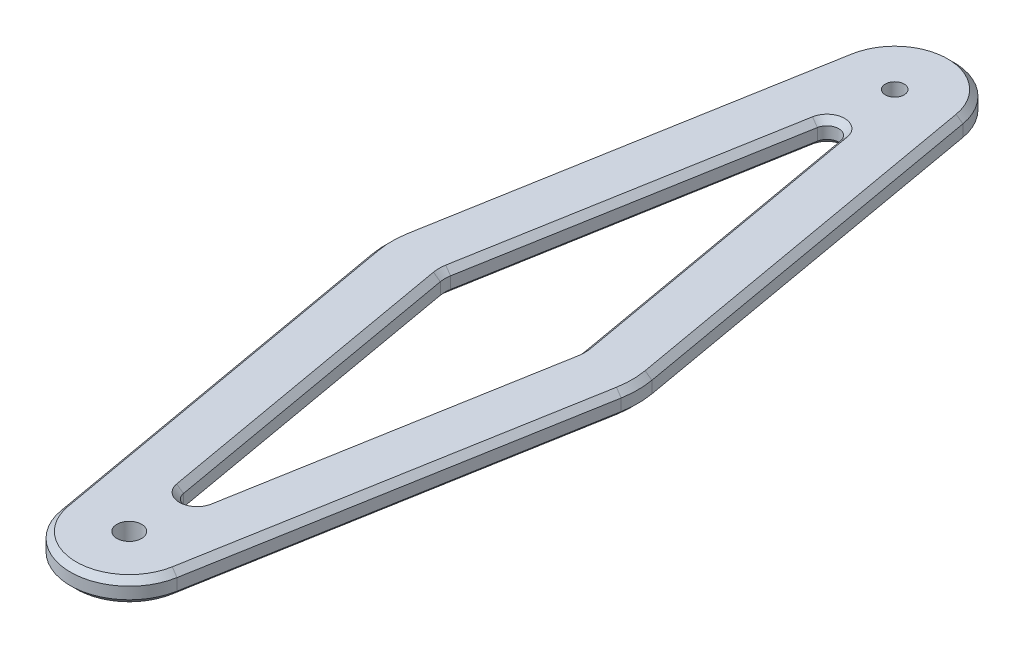
SolidWorks part; units mm, degrees
ref_plane "前视基准面" through (0, 0, 0) normal (0, 0, 1) x (1, 0, 0)
ref_plane "上视基准面" through (0, 0, 0) normal (0, 1, 0) x (1, 0, 0)
ref_plane "右视基准面" through (0, 0, 0) normal (1, 0, 0) x (0, 0, -1)
other "Configuration Table"
sketch "草图1" plane through (0, 0, 0) normal (0, 1, 0) x (1, 0, 0)
  line L0 (0, 0) -> (95.6592, 0) construction
  line L1 (0, 0) -> (0, 65) construction
  line L2 (-21.1562, 2.6047) -> (-9.8481, 66.7365)
  line L3 (21.1562, 2.6047) -> (9.8481, 66.7365)
  line L4 (21.1562, -2.6047) -> (9.8481, -66.7365)
  line L5 (-21.1562, -2.6047) -> (-9.8481, -66.7365)
  arc A0 (-9.8481, 66.7365) -> (9.8481, 66.7365) centre (0, 65) cw
  arc A1 (-9.8481, -66.7365) -> (9.8481, -66.7365) centre (0, -65) ccw
  arc A2 (21.1562, 2.6047) -> (21.1562, -2.6047) centre (6.3841, 0) cw
  arc A3 (-21.1562, 2.6047) -> (-21.1562, -2.6047) centre (-6.3841, 0) ccw
  point P14 (21.6155, 0)
  point P17 (-21.6155, 0)
  dimension "D2" = 65
  dimension "D3" = 10
  dimension "D4" = 15
  dimension "D1" = 80
extrude "凸台-拉伸1" add sketch "草图1" along normal mid plane 4
sketch "草图2" plane through (0, 2, 0) normal (0, 1, 0) x (1, 0, 0)
  circle A0 centre (0, 65) radius 1.6
  circle A1 centre (0, -65) radius 2.1
  dimension "D1" = 4.2
  dimension "D2" = 3.2
extrude "切除-拉伸1" cut sketch "草图2" against normal through all
sketch "草图6" plane through (0, 0, 0) normal (0, 1, 0) x (1, 0, 0)
  line L8 (0, 65) -> (-11.3082, 0.8682)
  line L9 (-11.3082, -0.8682) -> (0, -65)
  line L10 (0, -65) -> (11.3082, -0.8682)
  line L11 (11.3082, 0.8682) -> (0, 65)
  line L12 (-1.9696, 53.8298) -> (-11.3082, 0.8682)
  line L13 (-11.3082, -0.8682) -> (-1.9696, -53.8298)
  line L14 (1.9696, -53.8298) -> (11.3082, -0.8682)
  line L15 (11.3082, 0.8682) -> (1.9696, 53.8298)
  arc A4 (-1.9696, -53.8298) -> (1.9696, -53.8298) centre (0, -53.4825) ccw
  arc A5 (-1.9696, 53.8298) -> (1.9696, 53.8298) centre (0, 53.4825) cw
  arc A6 (-11.3082, 0.8682) -> (-11.3082, -0.8682) centre (-6.3841, 0) ccw
  arc A7 (-11.3082, 0.8682) -> (-11.3082, -0.8682) centre (-6.3841, 0) ccw
  arc A8 (11.3082, -0.8682) -> (11.3082, 0.8682) centre (6.3841, 0) ccw
  arc A9 (11.3082, -0.8682) -> (11.3082, 0.8682) centre (6.3841, 0) ccw
  dimension "D2" = 2
  dimension "D1" = 10
extrude "切除-拉伸4" cut sketch "草图6" against normal through all both and the other way through all
chamfer "倒角1" distance 1 angle 45 32 edges at (-15.5022, 2, -34.6706) (-21.3841, 2, 0) (0, 2, -75) (-15.5022, 2, 34.6706) (15.5022, 2, -34.6706) (0, 2, 75) (21.3841, 2, 0) (15.5022, 2, 34.6706) (-15.5022, -2, 34.6706) (0, -2, 75) (-21.3841, -2, 0) (15.5022, -2, 34.6706) (-15.5022, -2, -34.6706) (21.3841, -2, 0) (0, -2, -75) (15.5022, -2, -34.6706) (-6.6389, -2, 27.349) (-6.6389, -2, -27.349) (0, -2, 55.4825) (0, -2, -55.4825) (6.6389, -2, 27.349) (6.6389, -2, -27.349) (6.6389, 2, 27.349) (6.6389, 2, -27.349) (0, 2, 55.4825) (0, 2, -55.4825) (-6.6389, 2, 27.349) (-6.6389, 2, -27.349) (-11.3841, -2, 0) (11.3841, -2, 0) (11.3841, 2, 0) (-11.3841, 2, 0)
